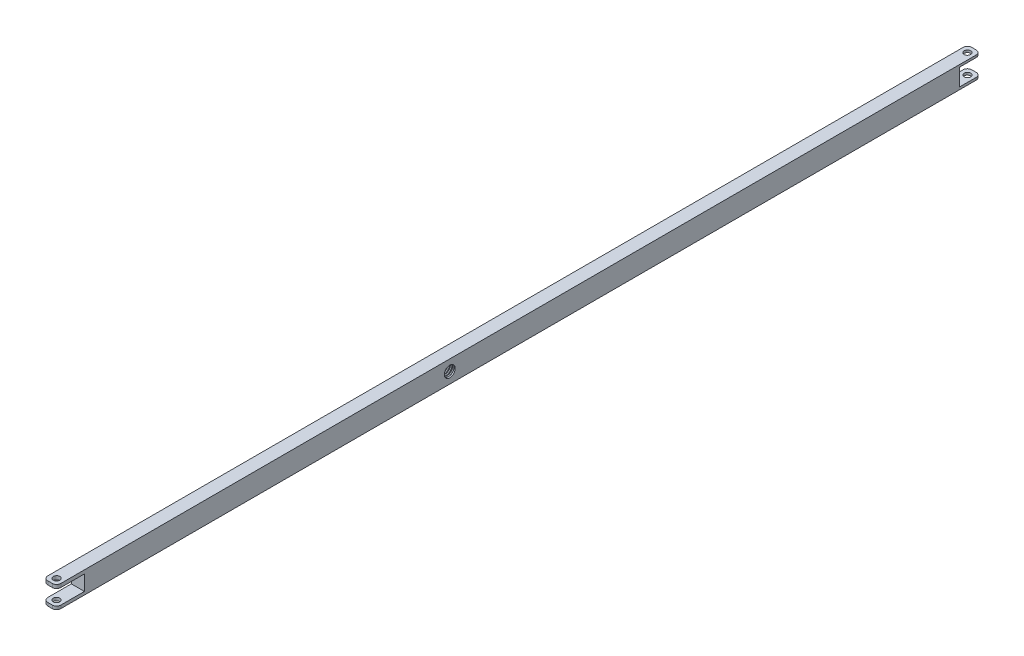
SolidWorks part; units mm, degrees
material "6063-T6"
ref_plane "Front Plane" through (0, 0, 0) normal (0, 0, 1) x (1, 0, 0)
ref_plane "Top Plane" through (0, 0, 0) normal (0, 1, 0) x (1, 0, 0)
ref_plane "Right Plane" through (0, 0, 0) normal (1, 0, 0) x (0, 0, -1)
sketch "Sketch1" plane through (0, 0, 0) normal (0, 0, 1) x (1, 0, 0)
  line L1 (0, 0) -> (7.62, 0)
  line L2 (0, 0) -> (0, 12.7)
  line L3 (0, 12.7) -> (7.62, 12.7)
  line L4 (7.62, 0) -> (7.62, 12.7)
  dimension "D1" = 7.62
  dimension "D2" = 12.7
extrude "Boss-Extrude1" add sketch "Sketch1" along normal blind 457.2
sketch "Sketch2" plane through (7.62, 0, 0) normal (1, 0, 0) x (0, 0, -1)
  line L0 (-457.2, 12.7) -> (0, 12.7) construction
  circle A0 centre (-7.3361, 12.45) radius 0.075
  dimension "D1" = 0.15
  dimension "D2" = 0.25
sketch "Sketch3" plane through (7.62, 0, 0) normal (1, 0, 0) x (0, 0, -1)
  line L0 (-457.2, 12.7) -> (0, 12.7) construction
  line L1 (-457.2, 0) -> (0, 0) construction
  line L2 (0, 0) -> (0, 12.7) construction
  line L3 (-457.2, 0) -> (-457.2, 12.7) construction
  circle A0 centre (-228.6, 6.35) radius 3.175
  dimension "D1" = 6.35
  dimension "D2" = 6.35
  dimension "D3" = 6.35
  dimension "D4" = 228.6
  dimension "D5" = 228.6
extrude "Cut-Extrude2" cut sketch "Sketch3" against normal blind 15
sketch "Sketch4" plane through (7.62, 0, 0) normal (1, 0, 0) x (0, 0, -1)
  line L0 (-457.2, 0) -> (-457.2, 12.7) construction
  line L1 (-457.2, 10.6365) -> (-441.013, 10.6365)
  line L2 (-457.2, 10.6365) -> (-457.2, 1.816)
  line L3 (-457.2, 1.816) -> (-441.013, 1.816)
  line L4 (-441.013, 10.6365) -> (-441.013, 1.816)
extrude "Cut-Extrude3" cut sketch "Sketch4" against normal blind 15
sketch "Sketch5" plane through (0, 12.7, 0) normal (0, 1, 0) x (1, 0, 0)
  line L0 (0, -457.2) -> (7.62, -449.58)
  line L1 (7.62, -457.2) -> (7.62, 0) construction
  circle A0 centre (3.81, -453.39) radius 1.9059
extrude "Cut-Extrude4" cut sketch "Sketch5" against normal blind 15 contours L0 A0 | L0 A0 region at (3.238, 12.7, 452.818) region at (4.382, 12.7, 453.962)
fillet "Fillet1" radius 2.5 4 edges at (0, 0.908, 457.2) (7.62, 0.908, 457.2) (7.62, 11.6682, 457.2) (0, 11.6682, 457.2)
sketch "Sketch6" plane through (0, 0, 0) normal (0, 0, -1) x (-1, 0, 0)
  line L4 (0, 0) -> (0, 12.7)
  line L5 (0, 12.7) -> (-7.62, 12.7)
  line L6 (-7.62, 12.7) -> (-7.62, 0)
  line L7 (-7.62, 0) -> (0, 0)
  line L8 (0, 0) -> (0, 12.7)
  line L9 (0, 12.7) -> (-7.62, 12.7)
  line L10 (-7.62, 12.7) -> (-7.62, 0)
  line L11 (-7.62, 0) -> (0, 0)
  dimension "D1" = 0
extrude "Boss-Extrude2" add sketch "Sketch6" along normal blind 80
sketch "Sketch7" plane through (7.62, 0, 0) normal (1, 0, 0) x (0, 0, -1)
  line L0 (80, 12.7) -> (80, 0) construction
  line L1 (80, 11.3649) -> (67.8669, 11.3649)
  line L2 (80, 11.3649) -> (80, 1.4267)
  line L3 (80, 1.4267) -> (67.8669, 1.4267)
  line L4 (67.8669, 11.3649) -> (67.8669, 1.4267)
extrude "Cut-Extrude5" cut sketch "Sketch7" against normal blind 80
sketch "Sketch8" plane through (0, 12.7, 0) normal (0, 1, 0) x (1, 0, 0)
  line L0 (0, 80) -> (7.62, 72.38)
  line L1 (7.62, -454.7) -> (7.62, 80) construction
  circle A1 centre (3.8916, 76.1084) radius 1.905
  dimension "D1" = 3.81
extrude "Cut-Extrude6" cut sketch "Sketch8" against normal blind 80 contours L0 A1 | L0 A1 region at (4.4633, 12.7, -76.6801) region at (3.3199, 12.7, -75.5367)
fillet "Fillet2" radius 2.5 4 edges at (0, 12.0324, -80) (7.62, 12.0324, -80) (7.62, 0.7133, -80) (0, 0.7133, -80)
thread "Thread1" pitch 1.27 method cut profile "Thread Profile1" start angle 0, offset 0, length 10, pitch 1.27, diameter 6.35
ref_plane "Plane1" through (7.62, 6.35, 231.775) normal (0, -1, 0) x (0, 0, 1)
sketch "Thread Profile1" plane through (7.62, 6.35, 231.775) normal (0, -1, 0) x (0, 0, 1)
  line L0 (0, 0) -> (0, 1.27) construction
  line L1 (0, 0) -> (0.6874, 0.3969)
  line L2 (0.6874, 0.3969) -> (0.6874, 0.5556)
  line L3 (0.6874, 0.5556) -> (0, 0.9525)
  line L4 (0.6874, 0.4762) -> (0, 0.4762) construction
  line L11 (0, 0) -> (0, 0.9525)
  point P2 (0, 0)
  dimension "Pitch" = 1.27
  dimension "Profile_Angle" = 60
  dimension "Profile_Land" = 0.1588
  dimension "Profile_Height" = 0.6874
